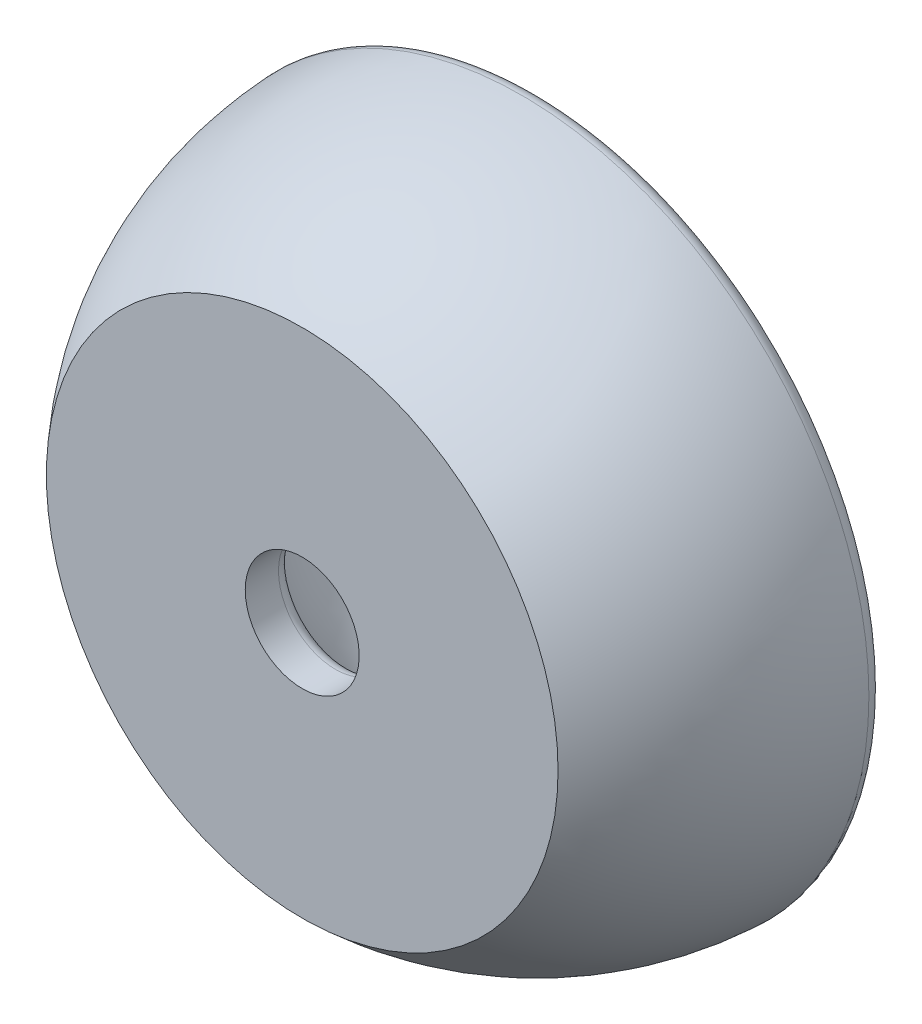
SolidWorks part; units mm, degrees
ref_plane "Front Plane" through (0, 0, 0) normal (0, 0, 1) x (1, 0, 0)
ref_plane "Top Plane" through (0, 0, 0) normal (0, 1, 0) x (1, 0, 0)
ref_plane "Right Plane" through (0, 0, 0) normal (1, 0, 0) x (0, 0, -1)
ref_axis "Polar Axis" through (0, 0, -14.3) along (0, 0, 1)
ref_axis "Solar Axis" through (-14.3, 0, 0) along (1, 0, 0)
sketch "Sketch2" plane through (0, 0, 0) normal (0, 1, 0) x (1, 0, 0)
  line L0 (5.6, 0) -> (9.75, 0)
  line L1 (10, 0.0987) -> (10.5, 0.0987) construction
  line L3 (0, -10.4013) -> (0, -9.4013) construction
  line L4 (1.6, -6.5906) -> (1.6, -5.3666)
  line L7 (0, 0) -> (0, -6.75) construction
  line L8 (1.6, -6.5906) -> (7.1851, -6.5906)
  line L10 (-1.6, -3.5906) -> (-0.923, -3.5906) construction
  line L11 (-1.6, -3.5906) -> (-1.6, -5.0979) construction
  line L15 (6.8458, -7.1906) -> (1.6, -7.1906) construction
  line L16 (1.6, -7.1906) -> (1.6, -8.1906) construction
  line L17 (3.9, -7.8894) -> (3.9, -9.7488) construction
  line L18 (4.7, -7.8894) -> (3.9, -7.8894) construction
  line L19 (4.7, -9.3894) -> (4.7, -7.8894) construction
  line L20 (1.6, -8.1906) -> (0, -9.4013) construction
  line L21 (4.7, -8.8267) -> (4.7, -9.3894) construction
  line L22 (0, 0) -> (0, -2.4) construction
  line L23 (-2.1, -0.2) -> (-2.1, 0) construction
  line L24 (-0.923, -3.5906) -> (-0.923, -1.9371) construction
  line L27 (-2.1, 0) -> (-5.45, 0) construction
  arc A0 (1.6, -5.3666) -> (5.6, 0) centre (0, 0) ccw
  circle A1 centre (0, 0) radius 2 construction
  arc A2 (7.1851, -6.5906) -> (9.75, 0) centre (0, 0) ccw
  arc A5 (3.9, -9.6501) -> (0, -10.4013) centre (0, 0.0987) cw construction
  arc A6 (10, 0.0987) -> (6.8458, -7.1906) centre (0, 0.0987) cw construction
  arc A7 (10.5, 0.0987) -> (4.7, -9.2906) centre (0, 0.0987) cw construction
  arc A8 (-1.25, -1.9371) -> (-2.1, -0.2) centre (0.1, -0.2) cw construction
  arc A9 (-1.6, -5.0979) -> (-5.3431, 0) centre (0, 0) cw construction
  line B0 (-1.5, -7.7906) -> (-1.5, -8.7906) construction
  line B1 (-1.5, -3.7906) -> (1.5, -3.7906) construction
  line B2 (-1.5, -3.7906) -> (-1.5, -7.7906) construction
  line B3 (-1.5, -7.7906) -> (1.5, -7.7906) construction
  line B4 (1.5, -3.7906) -> (1.5, -7.7906) construction
  line B5 (-1.5, -8.7906) -> (1.5, -8.7906) construction
  line B6 (1.5, -8.7906) -> (1.5, -7.7906) construction
  line B7 (0, -8.7906) -> (0, -3.7906) construction
  dimension "D2" = 7.1906
  dimension "D3" = 5.6
  dimension "D4" = 1.6
  dimension "D5" = 0.4
  dimension "D8" = 0.1
  dimension "D11" = 19.5
  dimension "D13" = 4
  dimension "D12" = 5.6
  dimension "D6" = 0.2
  dimension "D7" = 0.1
  dimension "D9" = 0.6
  dimension "D10" = 6.5906
sketch_block_instance "Block4-1"
sketch_block "Block4"
revolve "Main Body" add sketch "Sketch2" angle 360 about L7
fillet "Bottom Fillet" radius 0.4 2 edges at (-5.6, 0, 0) (-9.75, 0, 0)
fillet "Center Hole Fillet" radius 0.4 1 edges at (-1.6, 0, 5.3666)
